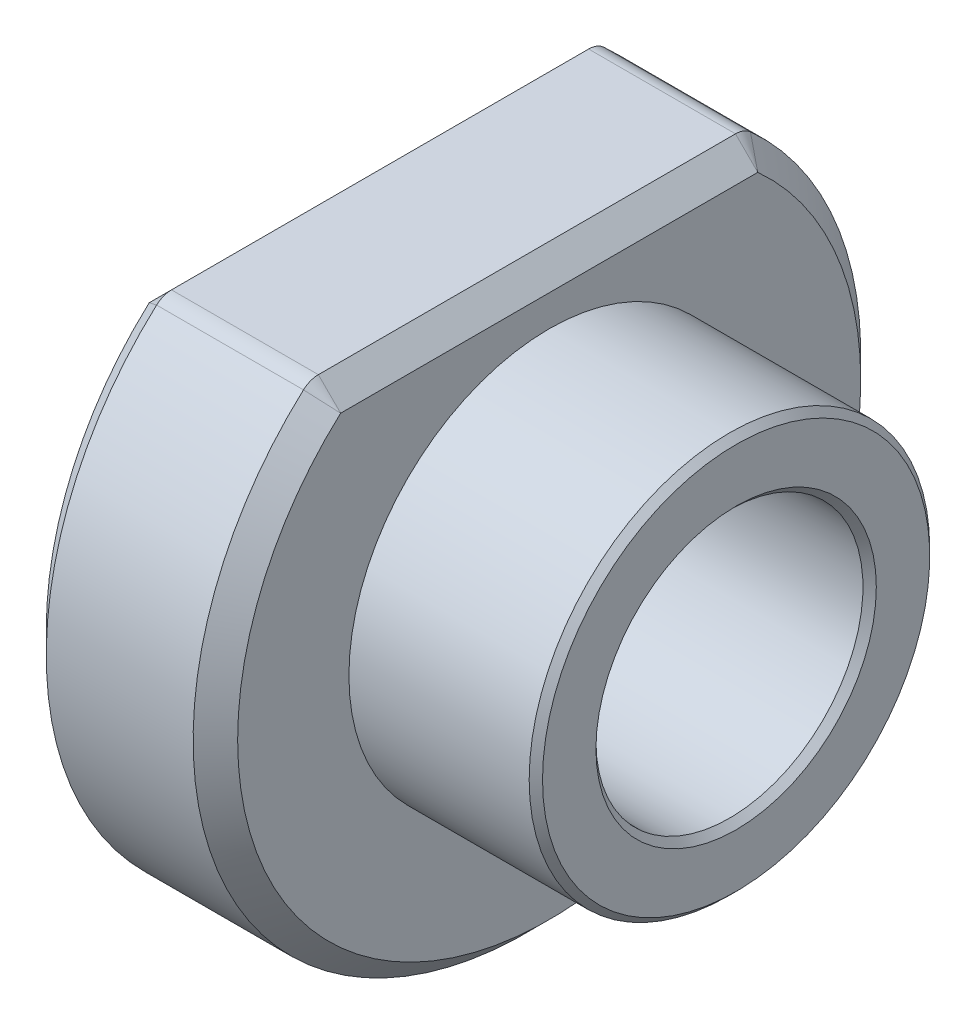
SolidWorks part; units mm, degrees
material "45"
ref_plane "前视基准面" through (0, 0, 0) normal (0, 0, 1) x (1, 0, 0)
ref_plane "上视基准面" through (0, 0, 0) normal (0, 1, 0) x (1, 0, 0)
ref_plane "右视基准面" through (0, 0, 0) normal (1, 0, 0) x (0, 0, -1)
sketch "草图1" plane through (0, 0, 0) normal (0, 0, 1) x (1, 0, 0)
  line L0 (0, 30) -> (0, 75)
  line L1 (0, 75) -> (43, 75)
  line L2 (43, 75) -> (43, 45)
  line L3 (43, 45) -> (85, 45)
  line L4 (85, 45) -> (85, 30)
  line L5 (85, 30) -> (0, 30)
  line L6 (0, 0) -> (85, 0) construction
  dimension "D1" = 43
  dimension "D2" = 75
  dimension "D3" = 45
  dimension "D4" = 30
  dimension "D5" = 85
revolve "旋转1" add sketch "草图1" angle 360 about L6
sketch "草图3" plane through (0, 0, 0) normal (-1, 0, 0) x (0, 0, 1)
  line L0 (-48.7442, 57) -> (48.7442, 57)
  circle A0 centre (0, 0) radius 75 construction
  circle A1 centre (0, 0) radius 30 construction
  circle A2 centre (0, 0) radius 75
  arc A6 (48.7442, 57) -> (-48.7442, 57) centre (0, 0) ccw
  dimension "D2" = 57
  dimension "D1" = 0
extrude "切除-拉伸1" cut sketch "草图3" against normal up to next
chamfer "倒角2" distance 1.5 angle 45 2 edges at (85, 0, 30) (85, 0, 45)
fillet "圆角1" radius 5 2 edges at (21.5, 57, 48.7442) (21.5, 57, -48.7442)
chamfer "倒角3" distance 5 angle 45 8 edges at (43, -75, 0) (0, -75, 0) (43, 57, 0) (43, 56.6675, -48.6543) (43, 56.6675, 48.6543) (0, 57, 0) (0, 56.6675, -48.6543) (0, 56.6675, 48.6543)
chamfer "倒角4" distance 2 angle 45 1 edges at (0, 0, 30)
